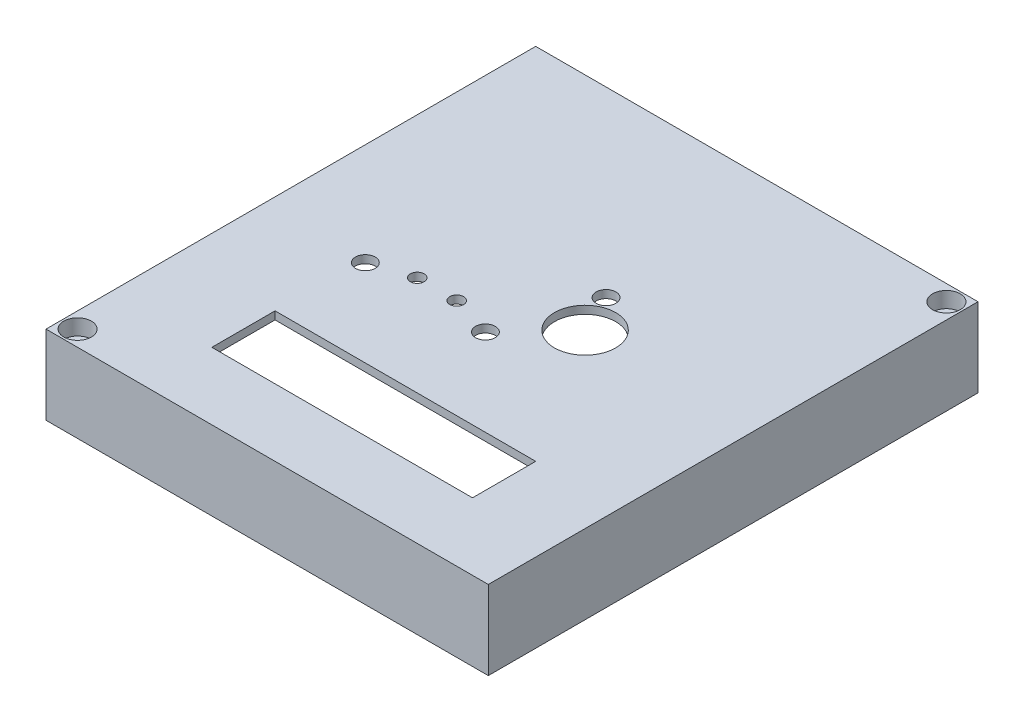
SolidWorks part; units mm, degrees
ref_plane "Front Plane" through (0, 0, 0) normal (0, 0, 1) x (1, 0, 0)
ref_plane "Top Plane" through (0, 0, 0) normal (0, 1, 0) x (1, 0, 0)
ref_plane "Right Plane" through (0, 0, 0) normal (1, 0, 0) x (0, 0, -1)
sketch "Sketch1" plane through (0, 0, 0) normal (0, 1, 0) x (1, 0, 0)
  line L1 (-56, -62) -> (56, -62)
  line L2 (-56, -62) -> (-56, 62)
  line L3 (-56, 62) -> (56, 62)
  line L4 (56, -62) -> (56, 62)
  line L5 (-56, -62) -> (56, 62) construction
  line L6 (-56, 62) -> (56, -62) construction
  point P0 (0, 0)
  dimension "D1" = 112
  dimension "D2" = 124
extrude "Boss-Extrude1" add sketch "Sketch1" along normal blind 2
sketch "Sketch4" plane through (0, 0, 0) normal (0, -1, 0) x (1, 0, 0)
  line L0 (-48, 58) -> (-48, 54)
  line L1 (-48, 54) -> (-52, 54)
  line L2 (48, -58) -> (48, -54)
  line L3 (48, -54) -> (52, -54)
  line L4 (56, -62) -> (56, 62)
  line L5 (56, 62) -> (-56, 62)
  line L6 (-56, 62) -> (-56, -62)
  line L7 (-56, -62) -> (56, -62)
  line L8 (56, -62) -> (56, 62)
  line L9 (56, 62) -> (-56, 62)
  line L10 (-56, 62) -> (-56, -62)
  line L11 (-56, -62) -> (56, -62)
  line L24 (52, -58) -> (52, 58)
  line L25 (52, 58) -> (-52, 58)
  line L26 (-52, 58) -> (-52, -58)
  line L27 (-52, -58) -> (52, -58)
  line L28 (52, -54) -> (52, 58)
  line L29 (52, 58) -> (-48, 58)
  line L30 (-52, 54) -> (-52, -58)
  line L31 (-52, -58) -> (48, -58)
  dimension "D4" = 4
  dimension "D6" = 4
  dimension "D1" = 0
  dimension "D2" = 4
extrude "Boss-Extrude2" add sketch "Sketch4" along normal blind 18
sketch "Sketch5" plane through (0, 2, 0) normal (0, 1, 0) x (1, 0, 0)
  line L0 (-56, -62) -> (56, -62) construction
  line L1 (-31, -45) -> (35, -45)
  line L2 (-31, -45) -> (-31, -29)
  line L3 (-31, -29) -> (35, -29)
  line L4 (35, -45) -> (35, -29)
  line L5 (-31, -45) -> (35, -29) construction
  line L6 (-31, -29) -> (35, -45) construction
  line L10 (-56, 62) -> (-56, -62) construction
  circle A0 centre (12.5, 6) radius 7.75
  circle A1 centre (-30.13, -7.01) radius 2.5
  circle A2 centre (-20.25, -3.7495) radius 1.75
  circle A3 centre (-10.25, -3.7495) radius 1.75
  circle A4 centre (0.2695, -7.01) radius 2.5
  circle A5 centre (8.001, 15.811) radius 2.5
  point P0 (2, -37)
  dimension "D4" = 15.5
  dimension "D8" = 5
  dimension "D9" = 3.5
  dimension "D5" = 47.999
  dimension "D6" = 46.189
  dimension "D10" = 43.5
  dimension "D12" = 55.7305
  dimension "D13" = 69.01
  dimension "D14" = 66.25
  dimension "D15" = 65.7495
  dimension "D16" = 65.7495
  dimension "D17" = 76.25
  dimension "D18" = 86.13
  dimension "D19" = 69.01
  dimension "D1" = 66
  dimension "D2" = 16
  dimension "D3" = 17
  dimension "D7" = 25
  dimension "D11" = 56
extrude "Cut-Extrude1" cut sketch "Sketch5" against normal up to next contours A0 | A4 | A3 | A2 | A1 | L1 L4 L3 L2 | A5 region at (2, 2, 37) region at (12.5, 2, -6) region at (-30.13, 2, 7.01) region at (-20.25, 2, 3.7495) region at (-10.25, 2, 3.7495) region at (0.2695, 2, 7.01) region at (8.001, 2, -15.811)
sketch "Sketch6" plane through (0, 2, 0) normal (0, 1, 0) x (1, 0, 0)
  line L0 (56, 62) -> (-56, 62) construction
  line L1 (56, -62) -> (56, 62) construction
  line L2 (-56, -62) -> (56, -62) construction
  line L3 (-56, 62) -> (-56, -62) construction
  circle A0 centre (52, 58) radius 2
  circle A1 centre (-52, -58) radius 2
  dimension "D1" = 4
  dimension "D4" = 4
  dimension "D2" = 4
  dimension "D3" = 4
  dimension "D5" = 4
  dimension "D6" = 4
extrude "Cut-Extrude2" cut sketch "Sketch6" against normal through all
sketch "Sketch7" plane through (0, 2, 0) normal (0, 1, 0) x (1, 0, 0)
  circle A0 centre (-52, -58) radius 3.5
  circle A1 centre (52, 58) radius 3.5
  dimension "D1" = 7
  dimension "D2" = 7
extrude "Cut-Extrude3" cut sketch "Sketch7" against normal blind 4
sketch "Sketch8" plane through (-56, 0, 0) normal (-1, 0, 0) x (0, 0, 1)
  line L7 (-49, -7.6872) -> (-39, -7.6872) construction
  line L8 (-49, -2.6872) -> (-39, -2.6872)
  line L9 (-49, -12.6872) -> (-39, -12.6872)
  line L10 (-28, -7.6872) -> (-18, -7.6872) construction
  line L11 (-28, -2.6872) -> (-18, -2.6872)
  line L12 (-28, -12.6872) -> (-18, -12.6872)
  line L13 (-8.5, -7.6872) -> (-3.5, -7.6872) construction
  line L14 (-8.5, -4.6872) -> (-3.5, -4.6872)
  line L15 (-8.5, -10.6872) -> (-3.5, -10.6872)
  line L16 (-62, 2) -> (-62, -18) construction
  arc A0 (-49, -2.6872) -> (-49, -12.6872) centre (-49, -7.6872) ccw
  arc A1 (-39, -12.6872) -> (-39, -2.6872) centre (-39, -7.6872) ccw
  arc A2 (-28, -2.6872) -> (-28, -12.6872) centre (-28, -7.6872) ccw
  arc A3 (-18, -12.6872) -> (-18, -2.6872) centre (-18, -7.6872) ccw
  arc A4 (-8.5, -4.6872) -> (-8.5, -10.6872) centre (-8.5, -7.6872) ccw
  arc A5 (-3.5, -10.6872) -> (-3.5, -4.6872) centre (-3.5, -7.6872) ccw
  point P2 (-44, -7.6872)
  point P8 (-23, -7.6872)
  point P15 (-6, -7.6872)
  point P23 (-54, -7.6872)
  point P24 (-34, -7.6872)
  dimension "D2" = 5
  dimension "D3" = 3
  dimension "D1" = 20
  dimension "D4" = 5
  dimension "D5" = 13
  dimension "D6" = 34
  dimension "D7" = 56
extrude "Cut-Extrude4" cut sketch "Sketch8" against normal blind 20
sketch "Sketch9" plane through (0, 0, -62) normal (0, 0, -1) x (-1, 0, 0)
  line L0 (-28, -10) -> (-38, -10) construction
  line L1 (-28, -12.5) -> (-38, -12.5)
  line L2 (-28, -7.5) -> (-38, -7.5)
  line L3 (-56, 2) -> (56, 2) construction
  line L4 (-56, 2) -> (-56, -18) construction
  arc A0 (-28, -12.5) -> (-28, -7.5) centre (-28, -10) ccw
  arc A1 (-38, -7.5) -> (-38, -12.5) centre (-38, -10) ccw
  point P2 (-33, -10)
  dimension "D2" = 2.5
  dimension "D1" = 10
  dimension "D3" = 12
  dimension "D4" = 23
extrude "Cut-Extrude5" cut sketch "Sketch9" against normal up to next
